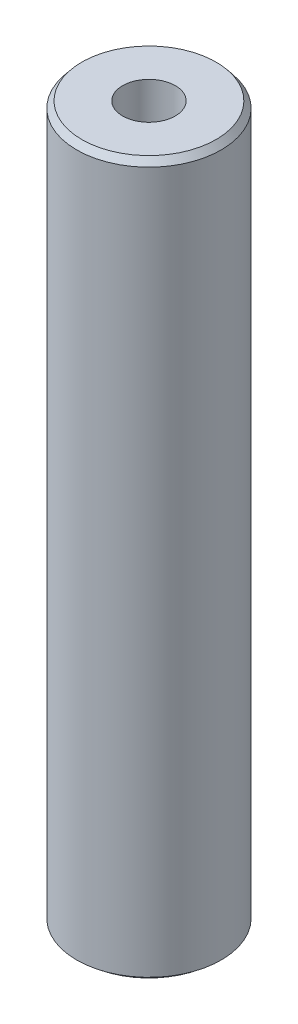
SolidWorks part; units mm, degrees
ref_plane "Front Plane" through (0, 0, 0) normal (0, 0, 1) x (1, 0, 0)
ref_plane "Top Plane" through (0, 0, 0) normal (0, 1, 0) x (1, 0, 0)
ref_plane "Right Plane" through (0, 0, 0) normal (1, 0, 0) x (0, 0, -1)
sketch "Sketch1" plane through (0, 0, 0) normal (0, 1, 0) x (1, 0, 0)
  circle A0 centre (0, 0) radius 57.5
  dimension "SHAFT_OD" = 115
extrude "Boss-Extrude1" add sketch "Sketch1" along normal blind 567.3937
sketch "Sketch2" plane through (0, 0, 0) normal (0, 1, 0) x (1, 0, 0)
  circle A0 centre (0, 0) radius 20.9452
  dimension "BORE_D" = 41.8904
extrude "Cut-Extrude1" cut sketch "Sketch2" along normal through all
chamfer "Chamfer1" distance 5.1 angle 38.684 2 edges at (0, 567.3937, 57.5) (0, 0, 57.5) first distance on face at (0, 567.3937, 57.5) first distance on face at (0, 0, 20.9452)
